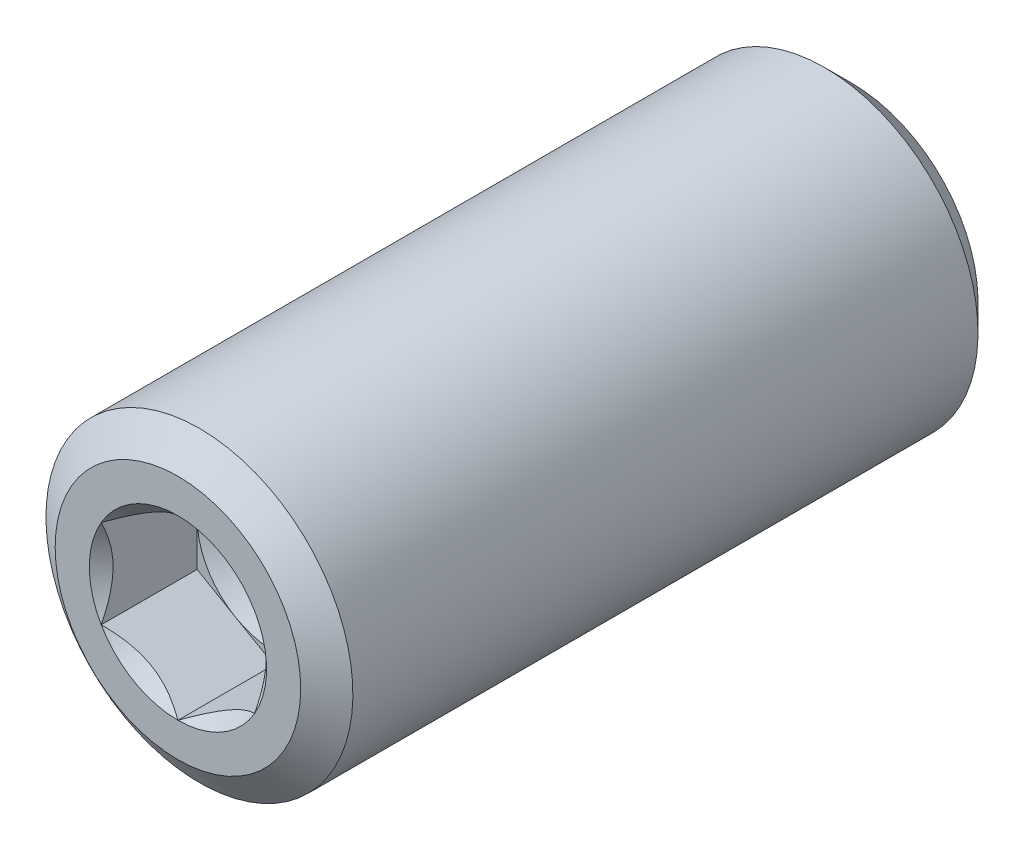
SolidWorks part; units mm, degrees
ref_plane "Front" through (0, 0, 0) normal (0, 0, 1) x (1, 0, 0)
ref_plane "Top" through (0, 0, 0) normal (0, 1, 0) x (1, 0, 0)
ref_plane "Right" through (0, 0, 0) normal (1, 0, 0) x (0, 0, -1)
sketch "Sketch22" plane through (0, 0, 0) normal (1, 0, 0) x (0, 0, -1)
  line L0 (-4.5, 0) -> (-4.5, 2)
  line L1 (-4.5, 2) -> (-4.1499, 2.5)
  line L2 (-4.1499, 2.5) -> (6.0331, 2.5)
  line L3 (6.0331, 2.5) -> (6.48, 2.0531)
  line L5 (4.5, 0) -> (-4.5, 0)
  line L6 (7.5, 0) -> (-4.5, 0) construction
  line L8 (6, 0) -> (6.48, 0) construction
  line L9 (-4.1499, -2.5) -> (6.0331, -2.5) construction
  line L10 (6.48, 2.0531) -> (6.48, 1.4211)
  line L11 (6.48, 0) -> (6.96, 0) construction
  arc A0 (6.48, 1.4211) -> (4.5, 0) centre (6, 0) ccw
  arc A1 (6.48, 1.4211) -> (7.5, 0) centre (6, 0) cw construction
  dimension "Tip dia" = 3
  dimension "Dia" = 5
  dimension "D3" = 35
  dimension "D7" = 4
  dimension "D1" = 45
  dimension "Length" = 12
  dimension "D2" = 0.48
revolve "Revolve1" add sketch "Sketch22" angle 360 about L6
sketch "Sketch32" plane through (0, 0, 0) normal (1, 0, 0) x (0, 0, -1)
  line L2 (7.5, 0) -> (-4.5, 0) construction
  line L3 (7.5, 0) -> (4.5, 0)
  arc A0 (6.48, 1.4211) -> (4.5, 0) centre (6, 0) ccw construction
  arc A1 (7.5, 0) -> (4.5, 0) centre (6, 0) ccw
revolve "Revolve2" add sketch "Sketch32" angle 360 mid plane about L3
ref_plane "Plane1" through (0, 0, -6.48) normal (0, 0, 1) x (1, 0, 0)
sketch "Sketch27" plane through (0, 0, -6.48) normal (0, 0, 1) x (1, 0, 0)
  circle A0 centre (0, 0) radius 2.5 construction
  circle A1 centre (0, 0) radius 2.5
curve "Helix/Spiral1" [suppressed] pitch 0.8 height 12.8 turns 16
sketch "Sketch28" plane through (0, 0, 0) normal (1, 0, 0) x (0, 0, -1)
  line L0 (6.48, 2.5) -> (7.18, 2.5)
  line L1 (7.18, 2.5) -> (6.88, 1.9804)
  line L2 (6.88, 1.9804) -> (6.78, 1.9804)
  line L3 (6.78, 1.9804) -> (6.48, 2.5)
  line L4 (6.63, 2.2402) -> (7.03, 2.2402) construction
  line L6 (-4.1499, 2.5) -> (6.0331, 2.5) construction
  line L7 (6.48, 2.2525) -> (6.48, -2.2525) construction
  dimension "D1" = 0.1
  dimension "D3" = 60
  dimension "D2" = 0.4
sweep "Cut-Sweep2" [suppressed] cut profiles "Sketch28" path "Helix/Spiral1"
sketch "Sketch23" plane through (0, 0, 4.5) normal (0, 0, 1) x (1, 0, 0)
  line L1 (0, 1.4434) -> (-1.25, 0.7217)
  line L2 (-1.25, 0.7217) -> (-1.25, -0.7217)
  line L3 (-1.25, -0.7217) -> (0, -1.4434)
  line L4 (0, -1.4434) -> (1.25, -0.7217)
  line L5 (1.25, -0.7217) -> (1.25, 0.7217)
  line L6 (1.25, 0.7217) -> (0, 1.4434)
  circle A0 centre (0, 0) radius 1.25 construction
  dimension "Hex" = 2.5
extrude "Cut-Extrude10" cut sketch "Sketch23" against normal blind 1.5625
sketch "Sketch24" plane through (0, 0, 4.5) normal (0, 0, 1) x (1, 0, 0)
  circle A0 centre (0, 0) radius 1.4434
extrude "Cut-Extrude11" cut sketch "Sketch24" against normal through all draft 45
sketch "Sketch26" plane through (0, 0, 2.9375) normal (0, 0, 1) x (1, 0, 0)
  circle A0 centre (0, 0) radius 1.25 construction
  circle A1 centre (0, 0) radius 1.25
extrude "Cut-Extrude12" cut sketch "Sketch26" against normal through all draft 60
sketch "Sketch30" plane through (0, 0, 0) normal (1, 0, 0) x (0, 0, -1)
  line L0 (-4.1499, 2.5) -> (6.0331, 2.5) construction
  line L1 (-4.5, 0) -> (-4.5, 2) construction
  line L2 (6, 1.5) -> (6, 0) construction
  line L3 (-4.1499, -2.5) -> (6.0331, -2.5) construction
  arc A0 (6.48, 1.4211) -> (4.5, 0) centre (6, 0) ccw construction
  point P0 (-4.5, 2.5)
  point P1 (7.5, 0.75)
  point P11 (0, -2.5)
  point P19 (6, 0.75)
sketch "Sketch31" plane through (0, 0, 0) normal (1, 0, 0) x (0, 0, -1)
  line L2 (6.48, 2.5) -> (6.48, -2.5) construction
  arc A0 (6.48, 1.4211) -> (4.5, 0) centre (6, 0) ccw construction
  arc A1 (6.48, 1.4211) -> (6.48, -1.4211) centre (6, 0) ccw
  circle A2 centre (6, 0) radius 1.5 construction
other "Move Face1" flip direction yes face at (0, 1.4211, -6.48) offset 0.05 parameters "D1"=0.05
equation "\"D7@Sketch22\"=\"Dia@Sketch22\"*.8"
equation "\"D1@Sketch28\" = \"D4@Helix/Spiral1\" * .125"
equation "\"D3@Helix/Spiral1\" = \"Length@Sketch22\" + \"D4@Helix/Spiral1\""
equation "\"hex Depth@Cut-Extrude10\" = \"Hex@Sketch23\" * .625"
equation "\"D2@Sketch28\" = \"D4@Helix/Spiral1\" * .5"
equation "\"D2@Sketch22\" = \"Tip dia@Sketch22\" * .16"
